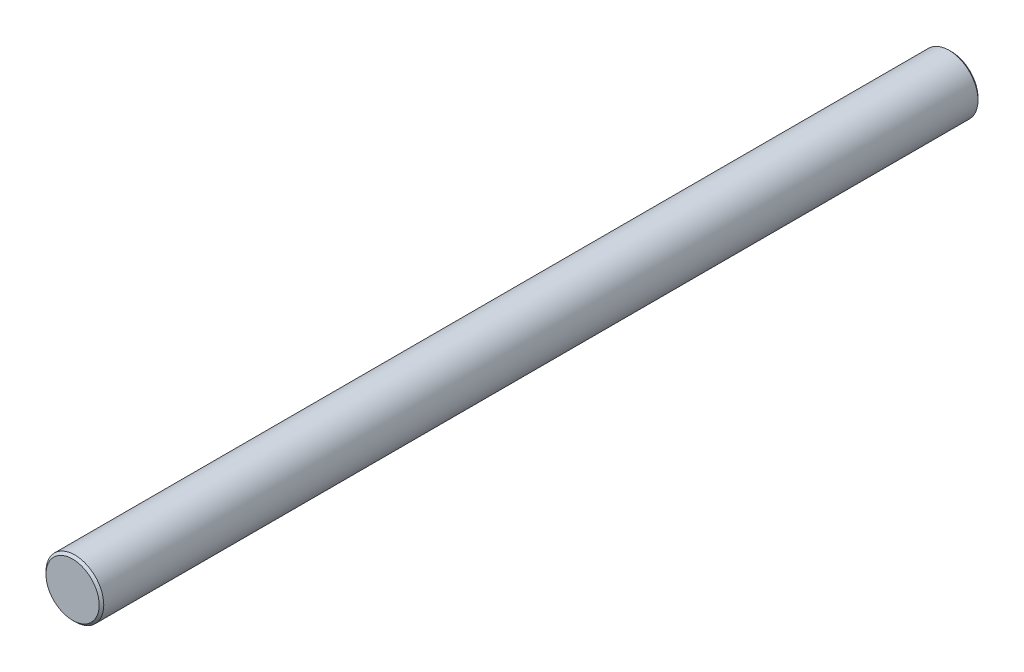
SolidWorks part; units mm, degrees
material "AISI 304"
ref_plane "Спереди" through (0, 0, 0) normal (0, 0, 1) x (1, 0, 0)
ref_plane "Сверху" through (0, 0, 0) normal (0, 1, 0) x (1, 0, 0)
ref_plane "Справа" through (0, 0, 0) normal (1, 0, 0) x (0, 0, -1)
ref_axis "ОсьX" through (-88.99, 0, 0) along (1, 0, 0)
ref_axis "ОсьZ" through (0, 55, 0) along (0, -1, 0)
ref_axis "ОсьY" through (0, 0, -88.99) along (0, 0, 1)
sketch "Эскиз1" plane through (0, 0, 0) normal (0, 0, 1) x (1, 0, 0)
  circle A0 centre (0, 0) radius 12.5
  dimension "D1" = 25
extrude "Бобышка-Вытянуть1" add sketch "Эскиз1" along normal mid plane 380
chamfer "Фаска1" distance 1 angle 45 2 edges at (12.5, 0, -190) (12.5, 0, 190)
